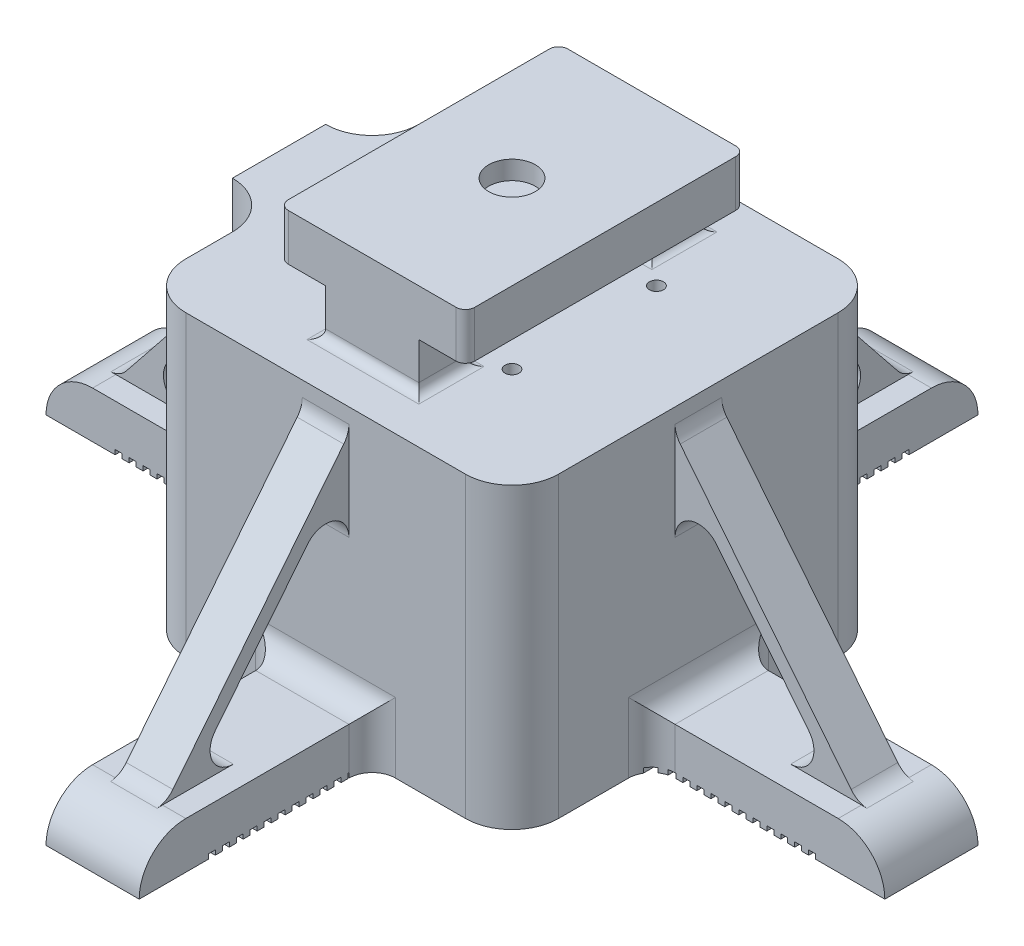
SolidWorks part; units mm, degrees
ref_plane "Front Plane" through (0, 0, 0) normal (0, 0, 1) x (1, 0, 0)
ref_plane "Top Plane" through (0, 0, 0) normal (0, 1, 0) x (1, 0, 0)
ref_plane "Right Plane" through (0, 0, 0) normal (1, 0, 0) x (0, 0, -1)
sketch "Sketch1" plane through (0, 0, 0) normal (0, 1, 0) x (1, 0, 0)
  line L1 (-40, 40) -> (40, 40)
  line L2 (-40, 40) -> (-40, -40)
  line L3 (-40, -40) -> (40, -40)
  line L4 (40, 40) -> (40, -40)
  line L5 (-40, 40) -> (40, -40) construction
  line L6 (-40, -40) -> (40, 40) construction
  point P0 (0, 0)
  dimension "D1" = 80
  dimension "D2" = 80
extrude "Boss-Extrude1" add sketch "Sketch1" along normal blind 14
sketch "Sketch2" plane through (0, 0, 0) normal (0, -1, 0) x (1, 0, 0)
  line L1 (-35, 35) -> (35, 35)
  line L2 (-35, 35) -> (-35, -35)
  line L3 (-35, -35) -> (35, -35)
  line L4 (35, 35) -> (35, -35)
  line L5 (-35, 35) -> (35, -35) construction
  line L6 (-35, -35) -> (35, 35) construction
  line L7 (-40, 40) -> (40, 40)
  line L8 (-40, 40) -> (-40, -40)
  line L9 (-40, -40) -> (40, -40)
  line L10 (40, 40) -> (40, -40)
  line L11 (-40, 40) -> (40, -40) construction
  line L12 (-40, -40) -> (40, 40) construction
  point P0 (0, 0)
  point P6 (0, 0)
  dimension "D1" = 5
  dimension "D2" = 5
extrude "Boss-Extrude2" add sketch "Sketch2" along normal blind 50
sketch "Sketch3" plane through (0, 0, 0) normal (0, -1, 0) x (1, 0, 0)
  circle A0 centre (-15.5, 15.5) radius 1.5
  circle A1 centre (15.5, 15.5) radius 1.5
  circle A2 centre (15.5, -15.5) radius 1.5
  circle A3 centre (-15.5, -15.5) radius 1.5
  dimension "D1" = 3
  dimension "D2" = 3
  dimension "D3" = 3
  dimension "D4" = 3
  dimension "D5" = 31
  dimension "D6" = 31
  dimension "D7" = 31
  dimension "D8" = 31
  dimension "D9" = 15.5
  dimension "D10" = 15.5
extrude "Cut-Extrude1" cut sketch "Sketch3" against normal blind 50
sketch "Sketch4" plane through (0, 0, 0) normal (0, -1, 0) x (1, 0, 0)
  circle A0 centre (0, 0) radius 2.75
  dimension "D1" = 5.5
extrude "Cut-Extrude2" cut sketch "Sketch4" against normal blind 50
sketch "Sketch5" plane through (40, 0, 0) normal (1, 0, 0) x (0, 0, -1)
  line L0 (40, -50) -> (-40, -50) construction
  line L1 (10, -50) -> (-10, -50)
  line L2 (10, -50) -> (10, -40)
  line L3 (10, -40) -> (-10, -40)
  line L4 (-10, -50) -> (-10, -40)
  line L5 (-40, 14) -> (-40, -50) construction
  dimension "D1" = 20
  dimension "D2" = 10
  dimension "D3" = 30
extrude "Boss-Extrude3" add sketch "Sketch5" along normal blind 50
sketch "Sketch7" plane through (0, -50, 0) normal (0, -1, 0) x (1, 0, 0)
  line L0 (90, 10) -> (40, 10) construction
  line L1 (85, 5) -> (40, 5)
  line L2 (85, 5) -> (85, -5)
  line L3 (85, -5) -> (40, -5)
  line L4 (40, 5) -> (40, -5)
  line L5 (90, -10) -> (40, -10) construction
  line L6 (90, 10) -> (90, -10) construction
  line L7 (35, -35) -> (35, 35) construction
  dimension "D1" = 5
  dimension "D2" = 5
  dimension "D3" = 5
  dimension "D4" = 5
extrude "Cut-Extrude3" cut sketch "Sketch7" against normal blind 5
sketch "Sketch8" plane through (0, -50, 0) normal (0, -1, 0) x (1, 0, 0)
  line L0 (90, 10) -> (40, 10) construction
  line L1 (37.6721, 10) -> (39.1721, 10)
  line L2 (37.6721, 10) -> (37.6721, 5)
  line L3 (37.6721, 5) -> (39.1721, 5)
  line L4 (39.1721, 10) -> (39.1721, 5)
  line L5 (85, 5) -> (40, 5) construction
  dimension "D1" = 1.5
extrude "Cut-Extrude4" cut sketch "Sketch8" against normal blind 1
pattern_linear "LPattern1" count 13 spacing 3 along (1, 0, 0) count 2 spacing 15 along (0, 0, -1) of "Cut-Extrude4"
pattern_circular "CirPattern10" count 4 over 360 about axis through (0, 0, 0) along (0, 1, 0) of "Boss-Extrude3"
fillet "Fillet3" radius 5 12 edges at (-10, -45, 40) (-40, -45, 10) (-40, -40, 0) (-40, -45, -10) (-10, -45, -40) (0, -40, -40) (10, -45, -40) (40, -45, -10) (40, -40, 0) (0, -40, 40) (40, -45, 10) (10, -45, 40)
pattern_circular "CirPattern11" count 4 over 360 about axis through (0, 0, 0) along (0, 1, 0) of "Cut-Extrude4", "LPattern1"
fillet "Fillet4" radius 10 4 edges at (0, -40, -90) (90, -40, 0) (0, -40, 90) (-90, -40, 0)
fillet "Fillet5" radius 10 4 edges at (40, -18, 40) (-40, -18, 40) (-40, -18, -40) (40, -18, -40)
sketch "Sketch9" plane through (0, 0, 0) normal (0, 0, 1) x (1, 0, 0)
  line L0 (-79.2, -40) -> (-40, 9)
  line L1 (-80, -40) -> (-45, -40) construction
  line L2 (-40, -50) -> (-40, 14) construction
  line L3 (-40, 9) -> (-40, 4)
  line L4 (-40, 4) -> (-75.2, -40)
  line L5 (-75.2, -40) -> (-79.2, -40)
  dimension "D1" = 4
  dimension "D2" = 5
  dimension "D3" = 5
  dimension "D4" = 10.8
extrude "Boss-Extrude4" add sketch "Sketch9" along normal mid plane 10
pattern_circular "CirPattern13" count 4 over 360 about axis through (0, 0, 0) along (0, 1, 0) of "Boss-Extrude4"
fillet "Fillet7" radius 5 16 edges at (79.2, -40, 0) (75.2, -40, 0) (40, 4, 0) (40, 9, 0) (0, 4, 40) (0, -40, 75.2) (0, -40, 79.2) (0, 9, 40) (-40, 9, 0) (-79.2, -40, 0) (0, 9, -40) (0, -40, -79.2) (0, -40, -75.2) (-75.2, -40, 0) (0, 4, -40) (-40, 4, 0)
sketch "Sketch10" plane through (0, 14, 0) normal (0, 1, 0) x (1, 0, 0)
  line L0 (30, 40) -> (-30, 40) construction
  circle A0 centre (-37.5, 0) radius 2.25
  dimension "D1" = 4.5
  dimension "D2" = 37.5
  dimension "D3" = 40
sketch "Sketch11" plane through (-40, 0, 0) normal (-1, 0, 0) x (0, 0, 1)
  line L0 (-30, 14) -> (30, 14) construction
  line L1 (-10, 14) -> (10, 14)
  line L2 (-10, 14) -> (-10, -11)
  line L3 (-10, -11) -> (10, -11)
  line L4 (10, 14) -> (10, -11)
  line L5 (5, 7.6304) -> (5, -38.2177) construction
  line L6 (-5, 7.6304) -> (-5, -38.2177) construction
  dimension "D1" = 5
  dimension "D2" = 5
  dimension "D3" = 25
extrude "Boss-Extrude5" add sketch "Sketch11" along normal blind 10
fillet "Fillet8" radius 10 3 edges at (-40, 1.5, 10) (-40, 1.5, -10) (-40, -11, 0)
extrude "Cut-Extrude5" cut sketch "Sketch10" against normal blind 5
sketch "Sketch12" plane through (0, 14, 0) normal (0, 1, 0) x (1, 0, 0)
  line L0 (30, 40) -> (-30, 40) construction
  line L1 (-10, 30) -> (10, 30)
  line L2 (-10, 30) -> (-10, 20)
  line L3 (-10, 20) -> (10, 20)
  line L4 (10, 30) -> (10, 20)
  line L5 (-10, -20) -> (10, -20)
  line L6 (-10, -20) -> (-10, -30)
  line L7 (-10, -30) -> (10, -30)
  line L8 (10, -20) -> (10, -30)
  line L9 (-30, -40) -> (30, -40) construction
  line L10 (40, -30) -> (40, 30) construction
  dimension "D1" = 20
  dimension "D2" = 20
  dimension "D3" = 10
  dimension "D4" = 10
  dimension "D5" = 30
  dimension "D6" = 30
  dimension "D7" = 10
  dimension "D8" = 10
extrude "Boss-Extrude6" add sketch "Sketch12" along normal blind 10
sketch "Sketch13" plane through (0, 24, 0) normal (0, 1, 0) x (1, 0, 0)
  line L0 (-10, 30) -> (-10, 20) construction
  line L5 (20, 30) -> (-20, 30)
  line L6 (20, 30) -> (20, -30)
  line L7 (20, -30) -> (-20, -30)
  line L8 (-20, 30) -> (-20, -30)
  line L9 (10, 20) -> (10, 30) construction
  dimension "D1" = 10
  dimension "D2" = 10
extrude "Boss-Extrude7" add sketch "Sketch13" along normal blind 10
sketch "Sketch14" plane through (0, 34, 0) normal (0, 1, 0) x (1, 0, 0)
  circle A0 centre (0, 0) radius 5
  dimension "D1" = 10
extrude "Cut-Extrude6" cut sketch "Sketch14" against normal blind 4
fillet "Fillet9" radius 2 12 edges at (-20, 29, -30) (20, 29, -30) (20, 29, 30) (-20, 29, 30) (-10, 14, -25) (0, 14, -30) (0, 14, 20) (10, 14, -25) (0, 14, -20) (10, 14, 25) (-10, 14, 25) (0, 14, 30)
